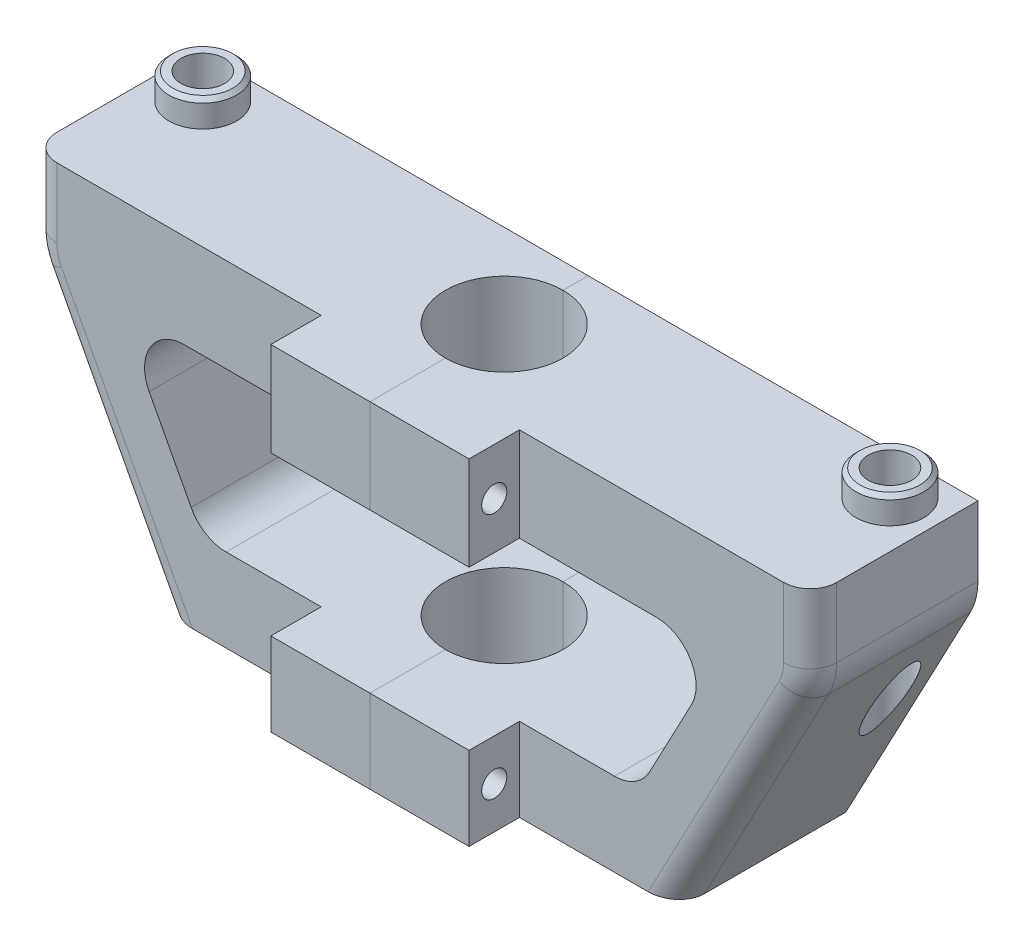
SolidWorks part; units mm, degrees
ref_plane "Front Plane" through (0, 0, 0) normal (0, 0, 1) x (1, 0, 0)
ref_plane "Top Plane" through (0, 0, 0) normal (0, 1, 0) x (1, 0, 0)
ref_plane "Right Plane" through (0, 0, 0) normal (1, 0, 0) x (0, 0, -1)
sketch "Sketch1" plane through (0, 0, 0) normal (0, 0, 1) x (1, 0, 0)
  line L0 (0, 0) -> (0, 26480.0211) construction
  line L1 (-29.5, 0) -> (29.5, 0)
  line L2 (29.5, 0) -> (29.5, -6.5)
  line L3 (29.5, -6.5) -> (19.5, -25.4)
  line L4 (19.5, -25.4) -> (-19.5, -25.4)
  line L5 (-19.5, -25.4) -> (-29.5, -6.5)
  line L6 (-29.5, -6.5) -> (-29.5, 0)
  point P5 (0, 0)
  point P10 (0, -25.4)
  dimension "D1" = 59
  dimension "D2" = 25.4
  dimension "D3" = 6.5
  dimension "D4" = 39
extrude "Boss-Extrude1" add sketch "Sketch1" along normal mid plane 12.7
sketch "Sketch8" plane through (0, 0, 0) normal (0, 1, 0) x (1, 0, 0)
  line L0 (29.5, -6.35) -> (-29.5, -6.35) construction
  line L1 (-7.5, -6.35) -> (7.5, -6.35)
  line L2 (-7.5, -6.35) -> (-7.5, -10.16)
  line L3 (-7.5, -10.16) -> (7.5, -10.16)
  line L4 (7.5, -6.35) -> (7.5, -10.16)
  point P4 (0, -6.35)
  dimension "D1" = 3.81
  dimension "D2" = 15
extrude "Boss-Extrude3" add sketch "Sketch8" against normal up to surface (25.4 mm away) contours L3 L4 L1 L2 up to face at (0, -25.4, 0)
sketch "Sketch2" plane through (0, 0, 0) normal (0, 0, 1) x (1, 0, 0)
  line L9 (-24.5502, -3.881) -> (-14.5502, -22.781)
  line L10 (-24.5502, -3.881) -> (-14.5502, -22.781) construction
  line L12 (-19.5, -19.1) -> (-7.5, -19.1)
  line L13 (-19.5, -19.1) -> (-7.5, -19.1) construction
  line L15 (14.5502, -22.781) -> (24.5502, -3.881)
  line L16 (14.5502, -22.781) -> (24.5502, -3.881) construction
  line L17 (-22.847, -7.1) -> (-16.4978, -19.1)
  line L18 (29.5, -7.1) -> (7.5, -7.1)
  line L19 (29.5, -7.1) -> (7.5, -7.1) construction
  line L20 (-16.4978, -19.1) -> (16.4978, -19.1)
  line L21 (16.4978, -19.1) -> (22.847, -7.1)
  line L22 (22.847, -7.1) -> (-22.847, -7.1)
  dimension "D1" = 5.6
  dimension "D2" = 6.3
  dimension "D3" = 5.6
  dimension "D4" = 7.1
extrude "Cut-Extrude1" cut sketch "Sketch2" against normal through all both and the other way through all
sketch "Sketch3" plane through (0, 0, 0) normal (0, 1, 0) x (1, 0, 0)
  circle A0 centre (0, 0) radius 4.45
  dimension "D1" = 8.9
extrude "Cut-Extrude2" cut sketch "Sketch3" against normal through all
fillet "Fillet1" radius 3 4 edges at (22.847, -7.1, 0) (16.4978, -19.1, 0) (-22.847, -7.1, 0) (-16.4978, -19.1, 0)
fillet "Fillet2" radius 5 2 edges at (29.5, -6.5, 0) (-29.5, -6.5, 0)
sketch "Sketch4" plane through (0, 0, 0) normal (0, 1, 0) x (1, 0, 0)
  line L0 (29.5, 6.35) -> (-29.5, 6.35) construction
  line L1 (0, 0) -> (0, 50000) construction
  circle A0 centre (-26, 3.19) radius 1.65
  circle A1 centre (-26, 3.19) radius 2.565
  circle A2 centre (26, 3.19) radius 1.65
  circle A3 centre (26, 3.19) radius 2.565
  dimension "D1" = 3.3
  dimension "D2" = 5.13
  dimension "D3" = 3.16
  dimension "D4" = 52
extrude "Boss-Extrude2" add sketch "Sketch4" along normal blind 2
sketch "Sketch5" plane through (0, 0, 0) normal (0, 1, 0) x (1, 0, 0)
  circle A0 centre (26, 3.19) radius 1.65 construction
  circle A1 centre (-26, 3.19) radius 1.65 construction
  circle A2 centre (26, 3.19) radius 1.65
  circle A3 centre (-26, 3.19) radius 1.65
extrude "Cut-Extrude3" cut sketch "Sketch5" against normal through all
sketch "Sketch6" plane through (0, 0, -6.35) normal (0, 0, -1) x (-1, 0, 0)
  line L0 (0, 0) -> (0, 50000) construction
  line L1 (17.75, -16.1) -> (-17.75, -16.1) construction
  line L2 (17.75, -19.1) -> (-17.75, -19.1)
  line L3 (17.75, -13.1) -> (-17.75, -13.1)
  line L4 (14.691, -19.1) -> (-14.691, -19.1) construction
  arc A0 (17.75, -19.1) -> (17.75, -13.1) centre (17.75, -16.1) ccw
  arc A1 (-17.75, -13.1) -> (-17.75, -19.1) centre (-17.75, -16.1) ccw
  point P5 (0, -16.1)
  dimension "D1" = 3
  dimension "D2" = 35.5
extrude "Cut-Extrude4" cut sketch "Sketch6" against normal blind 1
fillet "Fillet3" radius 2 6 edges at (24.2098, -16.4986, 6.35) (29.3527, -6.4634, 6.35) (-24.2098, -16.4986, 6.35) (-29.3527, -6.4634, 6.35) (29.5, -2.6294, 6.35) (-29.5, -2.6294, 6.35)
chamfer "Chamfer1" distance 0.3 angle 45 2 edges at (26, 2, -0.625) (-26, 2, -0.625)
hole_wizard "M2 Clearance Hole1" positions "Sketch11" profile "Sketch10" hole size "M2" standard "ANSI Metric" end condition through all
sketch "Sketch11" plane through (7.5, 0, 0) normal (1, 0, 0) x (0, 0, -1)
  line L0 (-6.35, 0) -> (-10.16, 0) construction
  line L1 (-10.16, -7.1) -> (-10.16, 0) construction
  line L2 (-10.16, -25.4) -> (-10.16, -19.1) construction
  point P0 (-8.255, -22.25)
  point P2 (-8.255, -3.55)
  point P4 (0, 0)
  point P7 (-8.255, 0)
  point P10 (-10.16, -3.55)
  point P11 (0, 0)
  point P14 (-10.16, -22.25)
sketch "Sketch10" plane through (7.5, -22.25, 8.255) normal (0, 1, 0) x (0, 0, -1)
  line L0 (0, 0) -> (0, 37)
  line L1 (0, 37) -> (0.95, 37)
  line L2 (0.95, 37) -> (0.95, 0)
  line L5 (0.95, 0) -> (0, 0)
  line L11 (0, -6.35) -> (0, 107.95) construction
  dimension "Thru Hole Dia." = 1.9
  dimension "Thru Hole Depth" = 37
ref_plane "Plane1" through (0, 0, 0) normal (1, 0, 0) x (0, 0, -1)
split "Split1" trim tools "Plane1" bodies to split 108 resulting bodies 109 110
